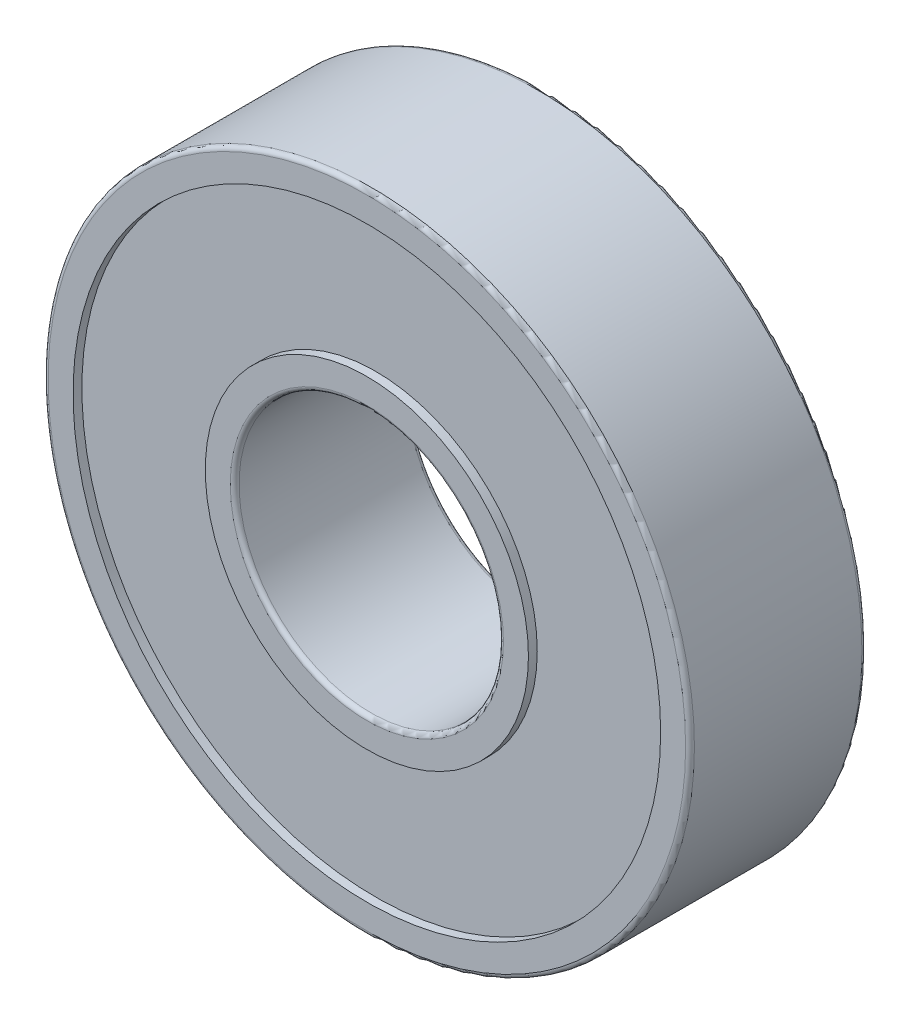
SolidWorks part; units mm, degrees
ref_plane "Front Plane" through (0, 0, 0) normal (0, 0, 1) x (1, 0, 0)
ref_plane "Top Plane" through (0, 0, 0) normal (0, 1, 0) x (1, 0, 0)
ref_plane "Right Plane" through (0, 0, 0) normal (1, 0, 0) x (0, 0, -1)
sketch "Sketch1" plane through (0, 0, 0) normal (0, 0, 1) x (1, 0, 0)
  circle A0 centre (0, 0) radius 4.5
  circle A1 centre (0, 0) radius 11
  dimension "D1" = 9
  dimension "D2" = 22
extrude "Boss-Extrude1" add sketch "Sketch1" along normal blind 6
sketch "Sketch2" plane through (0, 0, 6) normal (0, 0, 1) x (1, 0, 0)
  circle A3 centre (0, 0) radius 10
  circle A6 centre (0, 0) radius 5.5
  dimension "D1" = 11
  dimension "D2" = 20
extrude "Cut-Extrude1" cut sketch "Sketch2" against normal blind 0.3
extrude "Cut-Extrude2" cut sketch "Sketch2<2>" along normal blind 0.5 from surface starting at face at (11, 0, 0)
sketch "Sketch2<2>" plane through (0, 0, 6) normal (0, 0, 1) x (1, 0, 0) same geometry as "Sketch2"
fillet "Fillet1" radius 0.15 4 edges at (4.5, 0, 6) (11, 0, 6) (4.5, 0, 0) (11, 0, 0)
